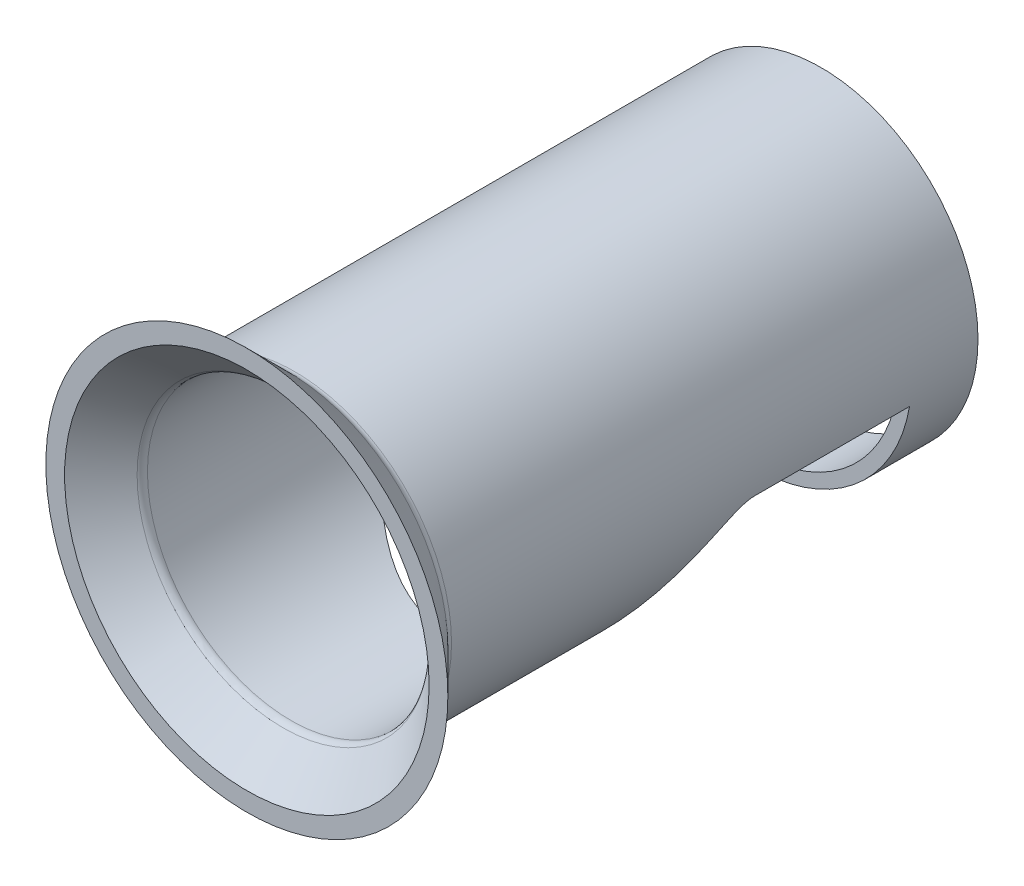
SolidWorks part; units mm, degrees
ref_plane "Piano frontale" through (0, 0, 0) normal (0, 0, 1) x (1, 0, 0)
ref_plane "Piano superiore" through (0, 0, 0) normal (0, 1, 0) x (1, 0, 0)
ref_plane "Piano destro" through (0, 0, 0) normal (1, 0, 0) x (0, 0, -1)
sketch "Schizzo1" plane through (0, 0, 0) normal (0, 0, 1) x (1, 0, 0)
  circle A0 centre (0, 0) radius 16.25
  circle A1 centre (0, 0) radius 17.75
  dimension "D1" = 32.5
  dimension "D2" = 1.5
extrude "Estrusione-Estrusione1" add sketch "Schizzo1" along normal blind 170
sketch "Schizzo2" plane through (0, 0, 0) normal (0, 1, 0) x (1, 0, 0)
  line L0 (17.75, 0) -> (-17.75, 0) construction
  line L1 (-17.5, -25) -> (-17.5, -7.5)
  line L2 (-17.5, -7.5) -> (17.5, -7.5)
  line L3 (17.5, -7.5) -> (17.5, -25)
  arc A0 (-17.5, -25) -> (17.5, -25) centre (0, -25) ccw
  point P10 (-16.3632, -26.1205)
  dimension "D1" = 35
  dimension "D2" = 25
extrude "Taglio-Estrusione1" cut sketch "Schizzo2" against normal blind 170
sketch "Schizzo4" plane through (0, 0, 0) normal (0, 0, -1) x (-1, 0, 0)
  circle A0 centre (0, 0) radius 41.7346
extrude "Taglio-Estrusione2" cut sketch "Schizzo4" against normal through all from offset 60 offset against normal yes
ref_plane "Piano1" through (0, 0, 65) normal (0, 0, 1) x (1, 0, 0)
sketch "Schizzo5" plane through (0, 0, 60) normal (0, 0, 1) x (1, 0, 0)
  circle A3 centre (0, 0) radius 17.75
  circle A4 centre (0, 0) radius 17.75
  dimension "D2" = 0
sketch "Schizzo6" plane through (0, 0, 65) normal (0, 0, 1) x (1, 0, 0)
  circle A0 centre (0, 0) radius 22.75
  circle A3 centre (0, 0) radius 17.75 construction
  dimension "D1" = 5
loft "Loft2" add profiles "Schizzo5", "Schizzo6" connector at (17.75, 0, 60) connector at (22.75, 0, 65)
sketch "Schizzo9" plane through (0, 0, 0) normal (0, 1, 0) x (1, 0, 0)
  line L0 (0, -53.81) -> (0, -67.4739)
  line L1 (0, -67.4739) -> (23.1025, -67.4739)
  line L2 (23.1025, -67.4739) -> (9.4387, -53.81)
  line L3 (9.4387, -53.81) -> (0, -53.81)
  line L4 (22.75, -65) -> (17.75, -60) construction
  dimension "D1" = 1.5
revolve "Taglia-Rivoluzione1" cut sketch "Schizzo9" angle 360 about L0
fillet "Raccordo1" radius 1 4 edges at (17.75, 0, 60) (-16.875, 0, 7.5) (16.875, 0, 7.5) (15.6287, 0, 60)
